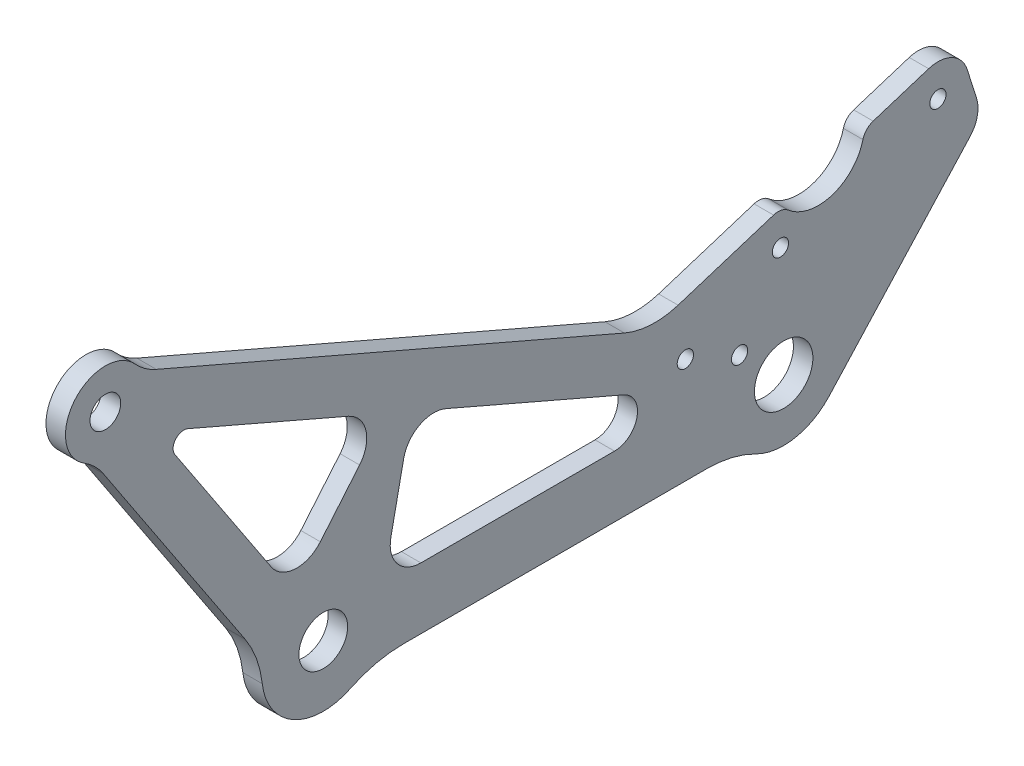
SolidWorks part; units mm, degrees
material "AISI 1020"
ref_plane "Front Plane" through (0, 0, 0) normal (0, 0, 1) x (1, 0, 0)
ref_plane "Top Plane" through (0, 0, 0) normal (0, 1, 0) x (1, 0, 0)
ref_plane "Right Plane" through (0, 0, 0) normal (1, 0, 0) x (0, 0, -1)
sketch "Sketch1" plane through (0, 0, 0) normal (1, 0, 0) x (0, 0, -1)
  line L0 (-60.7171, 0) -> (60.7171, 0)
  line L3 (0, -143.7223) -> (0, 143.7223) construction
  line L4 (-149.7529, 101.5535) -> (-94.5581, 18.1812)
  line L5 (-134.4049, 119.8783) -> (67.4524, 32.5212)
  line L6 (-75, 14) -> (75, 14) construction
  line L8 (-146, 114) -> (-75, 14) construction
  arc A20 (-134.4049, 119.8783) -> (-149.7529, 101.5535) centre (-146, 114) ccw
  arc A22 (-94.5581, 18.1812) -> (-60.7171, 0) centre (-75, 14) ccw
  arc A23 (60.7171, 0) -> (67.4524, 32.5212) centre (75, 14) ccw
  point P5 (0, 0)
  point P14 (0, 0)
  dimension "D3" = 20
  dimension "D5" = 13
  dimension "D6" = 20
  dimension "D4" = 127
  dimension "D7" = 254
  dimension "D10" = 6
  dimension "D11" = 6
  dimension "D9" = 3
  dimension "D12" = 3
  dimension "D13" = 6
  dimension "D14" = 6
  dimension "D2" = 150
  dimension "D8" = 122.6418
extrude "Boss-Extrude1" add sketch "Sketch1" along normal blind 6.35
hole_wizard "3/4 (0.75) Diameter Hole1" positions "Sketch4" profile "Sketch3" hole size "3/4" standard "ANSI Inch" end condition up to next
sketch "Sketch4" plane through (6.35, 0, 0) normal (1, 0, 0) x (0, 0, -1)
  point P5 (75, 14)
sketch "Sketch3" plane through (6.35, 14, -75) normal (0, 1, 0) x (0, 0, -1)
  line L0 (0, 0) -> (0, 6.35)
  line L1 (0, 6.35) -> (9.525, 6.35)
  line L2 (9.525, 6.35) -> (9.525, 0)
  line L5 (9.525, 0) -> (0, 0)
  line L11 (0, -6.35) -> (0, 107.95) construction
  dimension "Thru Hole Dia." = 19.05
  dimension "Thru Hole Depth" = 6.35
hole_wizard "Ø10.0 (10) Diameter Hole1" positions "Sketch9" profile "Sketch6" hole size "Ø10.0" standard "ANSI Metric" end condition up to next
sketch "Sketch9" plane through (6.35, 0, 0) normal (1, 0, 0) x (0, 0, -1)
  point P0 (-146, 114)
sketch "Sketch6" plane through (6.35, 114, 146) normal (0, 1, 0) x (0, 0, -1)
  line L0 (0, 0) -> (0, 6.35)
  line L1 (0, 6.35) -> (5, 6.35)
  line L2 (5, 6.35) -> (5, 0)
  line L5 (5, 0) -> (0, 0)
  line L11 (0, -6.35) -> (0, 107.95) construction
  dimension "Thru Hole Dia." = 10
  dimension "Thru Hole Depth" = 6.35
hole_wizard "Ø5/8\" Diameter Hole2" positions "Sketch16" profile "Sketch11" hole size "5/8" standard "ANSI Inch" end condition up to next
sketch "Sketch16" plane through (6.35, 0, 0) normal (1, 0, 0) x (0, 0, -1)
  line L0 (75, 14) -> (157.5513, 156.983)
  line L2 (0, 0) -> (0, 108.153) construction
  line L4 (-146, 114) -> (-119.4521, 194.8786)
  line L6 (-174.545, 70.324) -> (-178.0536, 59.6351) construction
  line L7 (-174.545, 70.324) -> (-178.0536, 59.6351) construction
  arc A0 (-94.5581, 18.1812) -> (-60.7171, 0) centre (-75, 14) ccw construction
  point P0 (-75, 14)
  dimension "D1" = 30
sketch "Sketch11" plane through (6.35, 14, 75) normal (0, 1, 0) x (0, 0, -1)
  line L0 (0, 0) -> (0, 6.35)
  line L1 (0, 6.35) -> (7.9375, 6.35)
  line L2 (7.9375, 6.35) -> (7.9375, 0)
  line L5 (7.9375, 0) -> (0, 0)
  line L11 (0, -6.35) -> (0, 107.95) construction
  dimension "Thru Hole Dia." = 15.875
  dimension "Thru Hole Depth" = 6.35
sketch "Sketch8" plane through (6.35, 0, 0) normal (1, 0, 0) x (0, 0, -1)
  line L2 (-54.5605, 67.8903) -> (-46.3008, 64.3157) construction
  line L3 (-52.9877, 32.028) -> (-48.7918, 52.2877)
  line L7 (-75.9573, 42.3434) -> (-63.1664, 57.6152)
  line L9 (-123.3455, 90.6494) -> (-91.9619, 43.2441)
  line L10 (-119.037, 95.7935) -> (-66.861, 73.2135)
  line L11 (19.8861, 20) -> (-43.1955, 20)
  line L12 (67.4524, 32.5212) -> (-134.4049, 119.8783) construction
  line L13 (-149.7529, 101.5535) -> (-94.5581, 18.1812) construction
  line L14 (-60.7171, 0) -> (60.7171, 0) construction
  line L15 (-84.5632, 32.0683) -> (-84.2827, 31.6447) construction
  line L16 (-55.4787, 20) -> (-55.9867, 20) construction
  line L17 (-54.5605, 67.8903) -> (-46.3008, 64.3157) construction
  line L18 (-35.0279, 59.4372) -> (22.8649, 34.3831)
  line L19 (-120.4271, 92.5814) -> (-104.3957, 79.1543) construction
  line L20 (19.8861, 27.5) -> (27.9693, 25.826) construction
  line L21 (-29.8567, 10) -> (10.3311, 10) construction
  arc A0 (-52.9877, 32.028) -> (-43.1955, 20) centre (-43.1955, 30) ccw
  arc A2 (-48.7918, 52.2877) -> (-35.0279, 59.4372) centre (-38.9996, 50.2597) cw
  arc A4 (-63.1664, 57.6152) -> (-66.861, 73.2135) centre (-70.8327, 64.0361) ccw
  arc A14 (-119.037, 95.7935) -> (-123.3455, 90.6494) centre (-120.4271, 92.5814) ccw
  arc A20 (-75.9573, 42.3434) -> (-91.9619, 43.2441) centre (-83.6236, 48.7643) cw
  arc A25 (-134.4049, 119.8783) -> (-149.7529, 101.5535) centre (-146, 114) ccw construction
  circle A27 centre (-146, 114) radius 5 construction
  arc A36 (-94.5581, 18.1812) -> (-60.7171, 0) centre (-75, 14) ccw construction
  circle A39 centre (-75, 14) radius 7.9375 construction
  arc A40 (19.8861, 20) -> (22.8649, 34.3831) centre (19.8861, 27.5) ccw
  circle A54 centre (-75, 14) radius 19.9375
  arc A55 (-55.9867, 20) -> (-84.2827, 31.6447) centre (-75, 14) ccw construction
  point P7 (-33.5049, 66.1162)
  point P19 (-33.4763, 76.1997)
  dimension "D8" = 8
  dimension "D9" = 12.0625
  dimension "D11" = 9
  dimension "D7" = 4
  dimension "D1" = 7
  dimension "D10" = 24.8576
  dimension "D2" = 15
  dimension "D12" = 10
  dimension "D13" = 14.6862
  dimension "D3" = 12
  dimension "D5" = 16
  dimension "D6" = 20
  dimension "D4" = 16
extrude "Cut-Extrude1" cut sketch "Sketch8" against normal up to next
fillet "Fillet1" radius 35 1 edges at (3.175, 18.1812, 94.5581)
fillet "Fillet3" radius 35 2 edges at (3.175, 32.5212, -67.4524) (3.175, 0, -60.7171)
fillet "Fillet4" radius 20 2 edges at (3.175, 101.5535, 149.7529) (3.175, 119.8783, 134.4049)
fillet "Fillet6" radius 40 1 edges at (3.175, 0, 60.7171)
sketch "Sketch17" plane through (0, 0, 0) normal (-1, 0, 0) x (0, 0, 1)
  line L0 (-31.692, 47.9971) -> (-74.6306, 61.6169)
  line L1 (-57.6351, 36.7697) -> (129.4114, 117.7173) construction
  line L2 (-134.8033, 70.2122) -> (-137.856, 60.5882)
  line L3 (-135.7084, 50.8215) -> (-89.7688, 0.5136)
  line L4 (-57.6351, 36.7697) -> (-31.692, 47.9971)
  line L6 (-84.0792, 16.8799) -> (-65.9208, 11.1201) construction
  line L7 (-100.5678, 75.614) -> (-71.9719, 66.5436) construction
  line L8 (-77.8799, 4.9208) -> (-72.1201, 23.0792) construction
  line L9 (-74.6306, 61.6169) -> (-101.2349, 70.0556) construction
  line L10 (-101.2349, 70.0556) -> (-122.2479, 76.7207)
  arc A0 (-73.7404, 33.9603) -> (-65.9164, -3.8182) centre (-75, 14) ccw construction
  arc A1 (-73.7404, 33.9603) -> (-57.6351, 36.7697) centre (-71.5361, 68.8908) ccw construction
  arc A2 (-73.7404, 33.9603) -> (-89.7688, 0.5136) centre (-75, 14) ccw
  arc A3 (-73.7404, 33.9603) -> (-57.6351, 36.7697) centre (-71.5361, 68.8908) ccw
  arc A4 (-137.856, 60.5882) -> (-135.7084, 50.8215) centre (-128.324, 57.5647) ccw
  arc A5 (-122.2479, 76.7207) -> (-134.8033, 70.2122) centre (-125.2713, 67.1887) ccw
  arc A6 (-101.2349, 70.0556) -> (-74.6306, 61.6169) centre (-86.2698, 71.0788) ccw
  circle A7 centre (-75, 14) radius 9.525 construction
  arc A8 (-71.9719, 66.5436) -> (-100.5678, 75.614) centre (-86.2698, 71.0788) ccw construction
  arc A9 (-100.5678, 75.614) -> (-101.2349, 70.0556) centre (-86.2698, 71.0788) ccw construction
  arc A10 (-74.6306, 61.6169) -> (-71.9719, 66.5436) centre (-86.2698, 71.0788) ccw construction
  point P15 (-75, 14)
  point P18 (-86.2698, 71.0788)
  point P26 (-139.6016, 55.0849)
  point P29 (-131.7798, 79.7442)
  point P31 (-75, 14)
  dimension "D5" = 10
  dimension "D1" = 41
  dimension "D2" = 45.5
  dimension "D3" = 120
  dimension "D4" = 74
  dimension "D6" = 30
  dimension "D7" = 51
  dimension "D8" = 28
extrude "Boss-Extrude2" add sketch "Sketch17" against normal up to surface (6.35 mm away) up to face at (6.35, 36.3112, 22.6592)
hole_wizard "M5 Clearance Hole1" positions "Sketch21" profile "Sketch19" hole size "M5" standard "ANSI Metric" end condition up to next
sketch "Sketch21" plane through (0, 0, 0) normal (-1, 0, 0) x (0, 0, 1)
  line L0 (-125.2509, 66.6577) -> (-73.9498, 50.3854) construction
  line L2 (-31.692, 47.9971) -> (-74.6306, 61.6169) construction
  line L3 (-75, 14) -> (-64.4178, 47.3619) construction
  line L5 (-134.8033, 70.2122) -> (-137.856, 60.5882) construction
  point P1 (-125.2509, 66.6577)
  point P3 (-73.9498, 50.3854)
  dimension "D1" = 35
  dimension "D2" = 10
  dimension "D3" = 53.82
sketch "Sketch19" plane through (0, 66.6577, -125.2509) normal (0, 1, 0) x (0, 0, 1)
  line L0 (0, 0) -> (0, 6.35)
  line L1 (0, 6.35) -> (2.65, 6.35)
  line L2 (2.65, 6.35) -> (2.65, 0)
  line L5 (2.65, 0) -> (0, 0)
  line L11 (0, -6.35) -> (0, 107.95) construction
  dimension "Thru Hole Dia." = 5.3
  dimension "Thru Hole Depth" = 6.35
fillet "Fillet7" radius 25 1 edges at (3.175, 47.9971, -31.692) type face fillet first side face at (3.175, 54.807, -53.1613) second side face at (3.175, 82.8572, 48.8597)
fillet "Fillet8" radius 5 2 edges at (3.175, 61.6169, -74.6306) (3.175, 70.0556, -101.2349)
sketch "Sketch22" plane through (6.35, 0, 0) normal (1, 0, 0) x (0, 0, -1)
  line L0 (0.2732, 61.5941) -> (-6.0815, 46.9101) construction
  line L1 (23.1137, 51.7095) -> (-129.4114, 117.7173) construction
  line L2 (22.8649, 34.3831) -> (-35.0279, 59.4372) construction
  line L3 (-2.9042, 54.2521) -> (70.5938, 22.4446) construction
  line L4 (70.5938, 22.4446) -> (60.6448, 26.7502) construction
  circle A0 centre (75, 14) radius 9.525 construction
  circle A1 centre (60.6448, 26.7502) radius 2.65
  dimension "D2" = 5.3
  dimension "D1" = 10.8408
extrude "Cut-Extrude2" cut sketch "Sketch22" against normal blind 10
sketch "Sketch24" plane through (6.35, 0, 0) normal (1, 0, 0) x (0, 0, -1)
  line L0 (12.6689, 56.2296) -> (6.3142, 41.5457) construction
  line L1 (23.1137, 51.7095) -> (-129.4114, 117.7173) construction
  line L2 (22.8649, 34.3831) -> (-35.0279, 59.4372) construction
  line L3 (9.4916, 48.8876) -> (70.5938, 22.4446) construction
  line L4 (60.6448, 26.7502) -> (42.969, 34.3997) construction
  circle A0 centre (75, 14) radius 9.525 construction
  circle A3 centre (42.969, 34.3997) radius 2.65
  dimension "D1" = 19.26
  dimension "D2" = 5.3
extrude "Cut-Extrude3" cut sketch "Sketch24" against normal blind 10
equation "\"D11@Sketch1\"=\"D10@Sketch1\""
equation "\"D12@Sketch1\"=\"D9@Sketch1\""
equation "\"D14@Sketch1\"=\"D13@Sketch1\""
